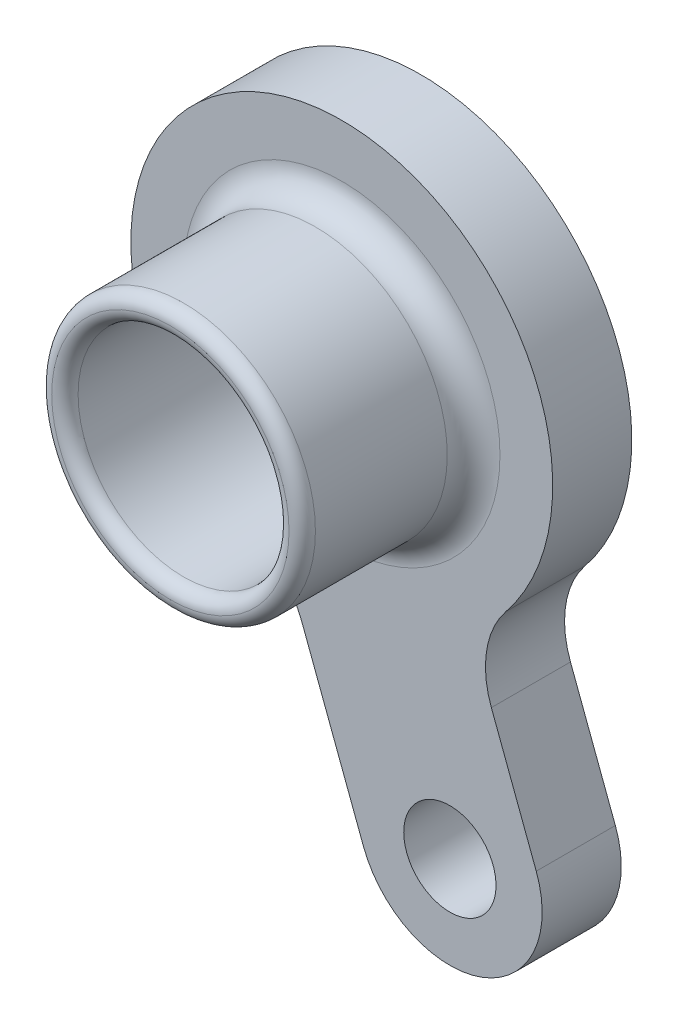
SolidWorks part; units mm, degrees
ref_plane "Plan de face" through (0, 0, 0) normal (0, 0, 1) x (1, 0, 0)
ref_plane "Plan de dessus" through (0, 0, 0) normal (0, 1, 0) x (1, 0, 0)
ref_plane "Plan de droite" through (0, 0, 0) normal (1, 0, 0) x (0, 0, -1)
sketch "Esquisse1" plane through (0, 0, 0) normal (0, 0, 1) x (1, 0, 0)
  circle A0 centre (0, 0) radius 5
  circle A1 centre (0, 0) radius 8
  dimension "D2" = 10
  dimension "D1" = 3
extrude "Boss.-Extru.1" add sketch "Esquisse1" along normal blind 3
sketch "Esquisse2" plane through (0, 0, 3) normal (0, 0, 1) x (1, 0, 0)
  circle A0 centre (0, 0) radius 4
  circle A1 centre (0, 0) radius 5
  circle A2 centre (0, 0) radius 5 construction
  dimension "D1" = 8
extrude "Boss.-Extru.2" add sketch "Esquisse2" along normal blind 6.5 and the other way blind 0.25
fillet "Congé2" radius 0.5 4 edges at (4, 0, 2.75) (5, 0, 2.75) (4, 0, 9.5) (5, 0, 9.5)
sketch "Esquisse4" plane through (0, 0, 0) normal (0, 0, 1) x (1, 0, 0)
  line L0 (-3.7398, -3.3187) -> (2.0575, -18.7187)
  line L1 (2.0575, -18.7187) -> (8.6087, -16.2525)
  line L2 (8.6087, -16.2525) -> (3.7398, -3.3187)
  line L3 (0, -14.21) -> (0, 0) construction
  line L4 (0, -14.21) -> (4.1, -14.21) construction
  line L5 (2.35, -14.21) -> (5.85, -14.21) construction
  line L6 (4.1, -14.21) -> (5.3331, -17.4856) construction
  line L7 (4.1, -14.21) -> (0.8244, -15.4431) construction
  line L8 (4.1, -14.21) -> (7.3756, -12.9769) construction
  circle A1 centre (0, 0) radius 5 construction
  circle A5 centre (4.1, -14.21) radius 1.75
  dimension "D1" = 14.21
  dimension "D2" = 4.1
  dimension "D3" = 3.5
extrude "Boss.-Extru.4" add sketch "Esquisse4" along normal blind 3
fillet "Congé3" radius 3.5 4 edges at (4.8775, -6.3411, 1.5) (-2.0812, -7.7245, 1.5) (2.0575, -18.7187, 1.5) (8.6087, -16.2525, 1.5)
fillet "Congé4" radius 1 1 edges at (5, 0, 3)
